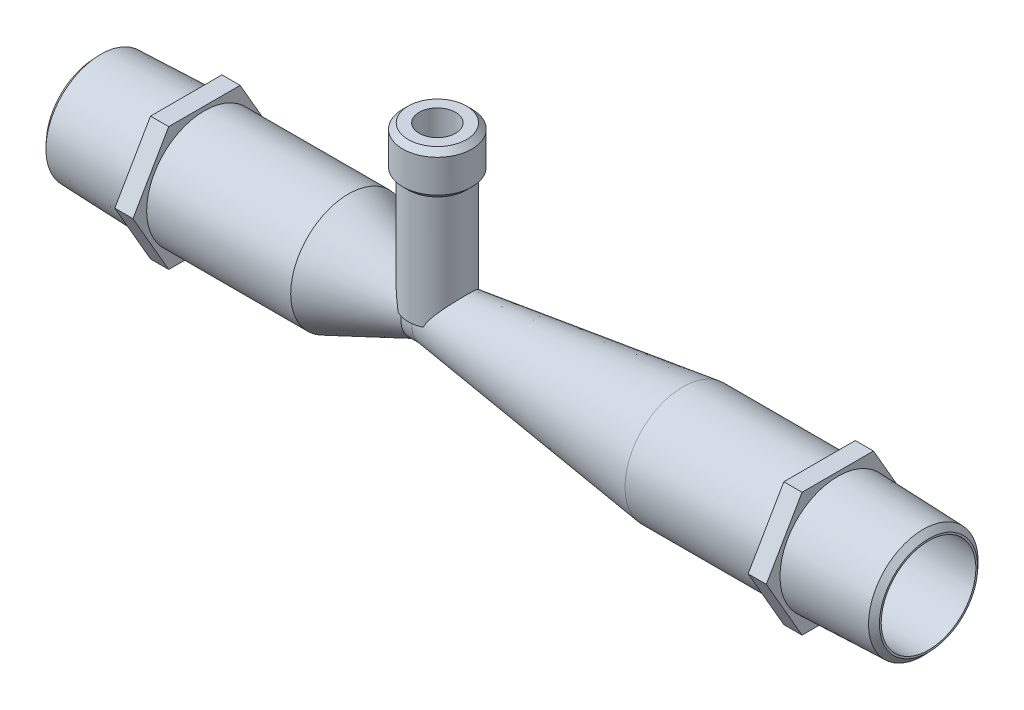
SolidWorks part; units mm, degrees
note: '?' marks a value the reader was unsure of. The reader was unsure of these and kept them because the rebuilt part matched: shared geometry of "Sketch7<2>".
material "PVC Rigid"
ref_plane "Front Plane" through (0, 0, 0) normal (0, 0, 1) x (1, 0, 0)
ref_plane "Top Plane" through (0, 0, 0) normal (0, 1, 0) x (1, 0, 0)
ref_plane "Right Plane" through (0, 0, 0) normal (1, 0, 0) x (0, 0, -1)
sketch "Sketch1" plane through (0, 0, 0) normal (0, 0, 1) x (1, 0, 0)
  line L0 (-94, 0) -> (0, 0) construction
  line L1 (0, 0) -> (135, 0) construction
  line L2 (-94, 15.002) -> (-69, 15.875)
  line L3 (-69, 15.875) -> (-24.4261, 15.875)
  line L4 (-24.4261, 15.875) -> (-3, 7)
  line L5 (-3, 7) -> (0, 7)
  line L6 (0, 7) -> (67.4123, 15.875)
  line L7 (67.4123, 15.875) -> (110, 15.875)
  line L8 (110, 15.875) -> (135, 15.002)
  dimension "D1" = 94
  dimension "D2" = 229
  dimension "D3" = 31.75
  dimension "D4" = 2
  dimension "D5" = 3
  dimension "D6" = 22.5
  dimension "D7" = 14
  dimension "D8" = 2
  dimension "D9" = 7.5
  dimension "D10" = 25
revolve "Revolve-Thin1" add sketch "Sketch1" angle 360 about L0
ref_plane "Plane1" through (-69, 0, 0) normal (1, 0, 0) x (0, 0, -1)
ref_plane "Plane2" through (110, 0, 0) normal (1, 0, 0) x (0, 0, -1)
sketch "Sketch2" plane through (-69, 0, 0) normal (1, 0, 0) x (0, 0, -1)
  line L1 (19.6299, 0) -> (9.815, 17)
  line L2 (9.815, 17) -> (-9.815, 17)
  line L3 (-9.815, 17) -> (-19.6299, 0)
  line L4 (-19.6299, 0) -> (-9.815, -17)
  line L5 (-9.815, -17) -> (9.815, -17)
  line L6 (9.815, -17) -> (19.6299, 0)
  circle A0 centre (0, 0) radius 17 construction
  circle A1 centre (0, 0) radius 13.0032
  circle A2 centre (0, 0) radius 13.0032 construction
  dimension "D1" = 34
extrude "Boss-Extrude1" add sketch "Sketch2" along normal blind 5
sketch "Sketch3" plane through (110, 0, 0) normal (1, 0, 0) x (0, 0, -1)
  line L1 (19.6299, 0) -> (9.815, 17)
  line L2 (9.815, 17) -> (-9.815, 17)
  line L3 (-9.815, 17) -> (-19.6299, 0)
  line L4 (-19.6299, 0) -> (-9.815, -17)
  line L5 (-9.815, -17) -> (9.815, -17)
  line L6 (9.815, -17) -> (19.6299, 0)
  circle A0 centre (0, 0) radius 17 construction
  circle A1 centre (0, 0) radius 13.0032
  circle A2 centre (0, 0) radius 13.0032 construction
extrude "Boss-Extrude2" add sketch "Sketch3" against normal blind 5
chamfer "Chamfer1" distance 1.5 angle 45 2 edges at (135, 0, 15.002) (-94, 0, 15.002)
sketch "Sketch4" plane through (0, 0, 0) normal (0, 1, 0) x (1, 0, 0)
  circle A0 centre (0, 0) radius 4
  dimension "D1" = 8
extrude "Cut-Extrude1" cut sketch "Sketch4" along normal up to next
sketch "Sketch5" plane through (0, 0, 0) normal (0, 0, 1) x (1, 0, 0)
  line L0 (0, 0) -> (0, 45) construction
  line L2 (-4, 0) -> (-8, 1.6569)
  line L4 (-8, 1.6569) -> (-8, 33)
  line L5 (-8, 33) -> (-9.5, 33)
  line L6 (-9.5, 33) -> (-9.5, 45)
  line L7 (-9.5, 45) -> (-5, 45)
  line L8 (-5, 45) -> (-5, 10.4142)
  line L9 (-5, 10.4142) -> (-4, 10)
  line L10 (-4, 10) -> (-4, 0)
  line L11 (-4, 7.4142) -> (-24.4261, 15.875) construction
  dimension "D1" = 16
  dimension "D2" = 19
  dimension "D3" = 10
  dimension "D4" = 10
  dimension "D5" = 45
  dimension "D6" = 4
  dimension "D8" = 12
revolve "Revolve3" add sketch "Sketch5" angle 360 about L0
chamfer "Chamfer2" distance 1.5 angle 45 2 edges at (0, 33, -9.5) (0, 45, -9.5)
sketch "Sketch6" plane through (0, 0, 0) normal (0, 0, 1) x (1, 0, 0)
  line L0 (-64, 17.875) -> (-3, 17.875)
  line L3 (0, 1.1997) -> (-24.4261, 15.875)
  line L5 (-24.4261, 15.875) -> (-64, 15.875)
  line L6 (-64, 17) -> (-64, 0) construction
  line L7 (-64, 15.875) -> (-64, 17.875)
  line L9 (105, 17.875) -> (-3, 17.875)
  line L11 (0, 1.1997) -> (105, 15.875)
  line L14 (105, 17) -> (105, 0) construction
  line L15 (105, 15.875) -> (105, 17.875)
  spline S0 degree 3 poles (3.3677, 1.6569) (2.2534, 1.4258) (1.133, 1.2582) (0, 1.1997) knots 0 0 0 0 1 1 1 1 construction
  dimension "D1" = 2
extrude "Boss-Extrude3" [suppressed] add sketch "Sketch6" along normal mid plane 2 separate body
pattern_circular "CirPattern2" [suppressed] count 4 over 360
other "CPoint1" parameters "Diameter"=12.7, "StubLength"=114.3
ref_axis "Axis1" through (-72.5009, 0, 0) along (1, 0, 0)?
other "CPoint2" parameters "Diameter"=12.7, "StubLength"=114.3
ref_axis "Axis2" through (94.5009, 0, 0) along (-1, 0, 0)?
other "CPoint3" parameters "Diameter"=19.05, "StubLength"=19.05
ref_axis "Axis3" through (-56, 0, 0) along (1, 0, 0)?
other "CPoint4" parameters "Diameter"=19.05, "StubLength"=19.05
ref_axis "Axis4" through (78, 0, 0) along (-1, 0, 0)?
other "CPoint5" parameters "Diameter"=25.4, "StubLength"=28.575
ref_axis "Axis5" through (120, 0, 0) along (-1, 0, 0)?
other "CPoint6" parameters "Diameter"=25.4, "StubLength"=28.575
ref_axis "Axis6" through (-79, 0, 0) along (1, 0, 0)?
other "CPoint7" parameters "Diameter"=12.7, "StubLength"=38.1
ref_axis "Axis7" through (0, 53.5, 0) along (0, -1, 0)?
sketch "Sketch7" plane through (0, 0, 0) normal (1, 0, 0) x (0, 0, -1)
  circle A1 centre (0, 0) radius 5
extrude "Cut-Extrude2" cut sketch "Sketch7" against normal blind 10 draft 14 draft outward yes
extrude "Cut-Extrude3" cut sketch "Sketch7<2>" along normal blind 10 draft 7 draft outward yes
sketch "Sketch7<2>" plane through (0, 0, 0) normal (1, 0, 0) x (0, 0, -1) same geometry as "Sketch7"
scale "Scale1" scale about centroid uniform scaling yes scale factor 2
ref_axis "Axis8" through (-18.6807, 62.5921, 0) along (0, -1, 0)?
other "RPoint1"
ref_axis "Vertical" through (-18.6807, 62.5921, 0) along (0, -1, 0)?
